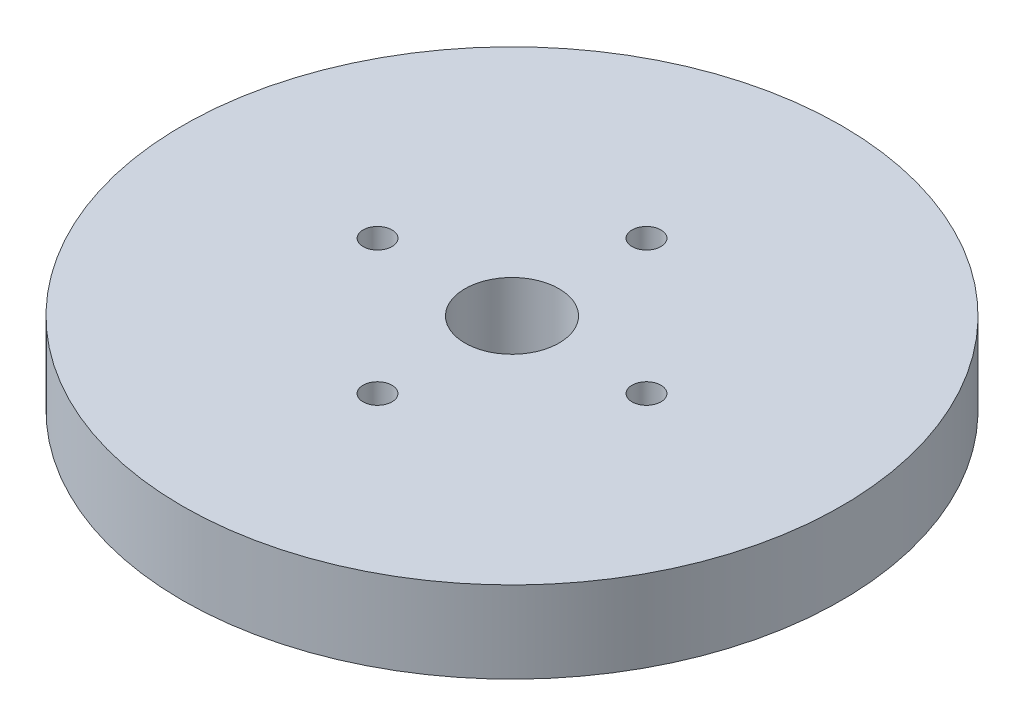
SolidWorks part; units mm, degrees
ref_plane "Front Plane" through (0, 0, 0) normal (0, 0, 1) x (1, 0, 0)
ref_plane "Top Plane" through (0, 0, 0) normal (0, 1, 0) x (1, 0, 0)
ref_plane "Right Plane" through (0, 0, 0) normal (1, 0, 0) x (0, 0, -1)
sketch "Sketch1" plane through (0, 0, 0) normal (0, 1, 0) x (1, 0, 0)
  circle A0 centre (0, 0) radius 52.5
  dimension "FLANGE_OD" = 105
extrude "Boss-Extrude1" add sketch "Sketch1" along normal blind 13
sketch "Sketch2" plane through (0, 0, 0) normal (0, 1, 0) x (1, 0, 0)
  circle A0 centre (0, 0) radius 7.5
  dimension "BORE_D" = 15
extrude "Cut-Extrude1" cut sketch "Sketch2" along normal through all
sketch "Sketch3" plane through (0, 13, 0) normal (0, 1, 0) x (1, 0, 0)
  circle A0 centre (0, 0) radius 21.4229 construction
  circle A1 centre (-21.4229, 0) radius 2.3052
  dimension "BOLT_D" = 4.6103
  dimension "BOLT_PCD" = 42.8459
extrude "Cut-Extrude2" cut sketch "Sketch3" against normal blind 8.843
pattern_circular "CirPattern1" count 4 over 360 about axis through (0, 0, 0) along (0, 1, 0) of "Cut-Extrude2"
